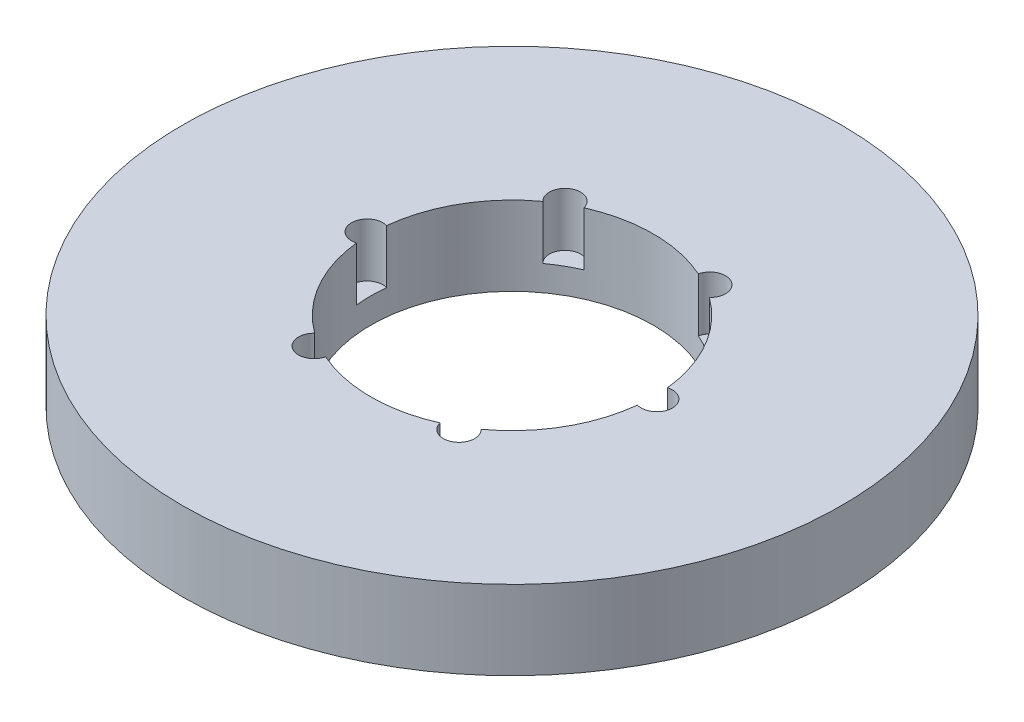
SolidWorks part; units mm, degrees
ref_plane "Front Plane" through (0, 0, 0) normal (0, 0, 1) x (1, 0, 0)
ref_plane "Top Plane" through (0, 0, 0) normal (0, 1, 0) x (1, 0, 0)
ref_plane "Right Plane" through (0, 0, 0) normal (1, 0, 0) x (0, 0, -1)
sketch "Sketch1" plane through (0, 0, 0) normal (0, 1, 0) x (1, 0, 0)
  circle A0 centre (0, 0) radius 87.5
  dimension "FLANGE_OD" = 175
extrude "Boss-Extrude1" add sketch "Sketch1" along normal blind 21
sketch "Sketch2" plane through (0, 0, 0) normal (0, 1, 0) x (1, 0, 0)
  circle A0 centre (0, 0) radius 37.5
  dimension "BORE_D" = 75
extrude "Cut-Extrude1" cut sketch "Sketch2" along normal through all
sketch "Sketch3" plane through (0, 21, 0) normal (0, 1, 0) x (1, 0, 0)
  circle A0 centre (0, 0) radius 38.4537 construction
  circle A1 centre (-38.4537, 0) radius 4.1545
  dimension "BOLT_D" = 8.309
  dimension "BOLT_PCD" = 76.9074
extrude "Cut-Extrude2" cut sketch "Sketch3" against normal blind 14.2685
pattern_circular "CirPattern1" count 6 over 360 about axis through (0, 0, 0) along (0, 1, 0) of "Cut-Extrude2"
